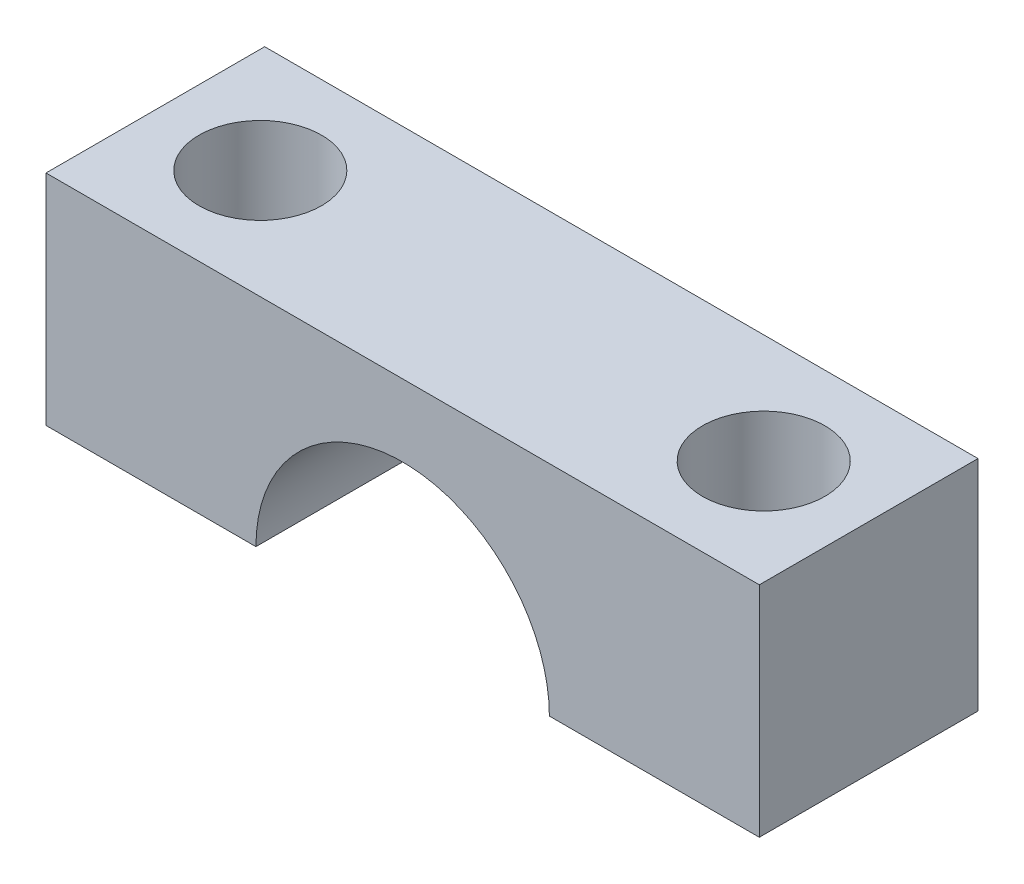
SolidWorks part; units mm, degrees
material "6061-T6 (SS)"
ref_plane "Front Plane" through (0, 0, 0) normal (0, 0, 1) x (1, 0, 0)
ref_plane "Top Plane" through (0, 0, 0) normal (0, 1, 0) x (1, 0, 0)
ref_plane "Right Plane" through (0, 0, 0) normal (1, 0, 0) x (0, 0, -1)
sketch "Sketch1" plane through (0, 0, 0) normal (0, 0, 1) x (1, 0, 0)
  line L1 (-8.155, -2.5) -> (8.155, -2.5)
  line L2 (-8.155, -2.5) -> (-8.155, 2.5)
  line L3 (-8.155, 2.5) -> (8.155, 2.5)
  line L4 (8.155, -2.5) -> (8.155, 2.5)
  line L5 (-8.155, -2.5) -> (8.155, 2.5) construction
  line L6 (-8.155, 2.5) -> (8.155, -2.5) construction
  point P0 (0, 0)
  dimension "D1" = 5
  dimension "D2" = 16.31
sketch "Sketch3" plane through (0, 0, 0) normal (0, 0, 1) x (1, 0, 0)
  line L0 (0, 0) -> (0, -2.5) construction
  line L1 (-8.155, -2.5) -> (8.155, -2.5) construction
  line L2 (-3.355, -2.5) -> (3.355, -2.5)
  line L3 (0, 0.855) -> (0, 2.5) construction
  line L4 (-8.155, 2.5) -> (8.155, 2.5) construction
  arc A0 (3.355, -2.5) -> (-3.355, -2.5) centre (0, -2.5) ccw
  point P8 (0, -2.5)
extrude "Boss-Extrude3" add sketch "Sketch1" against normal blind 5 contours L2 L3 L4 L1
extrude "Cut-Extrude9" cut sketch "Sketch3" against normal blind 5
sketch "Sketch4" plane through (0, 0, 0) normal (0, 1, 0) x (1, 0, 0)
  line L0 (0, 0) -> (0, 5) construction
  line L1 (-8.155, 0) -> (8.155, 0) construction
  line L2 (-8.155, 5) -> (8.155, 5) construction
  line L3 (0, 2.5) -> (5.755, 2.5) construction
  line L5 (0, 2.5) -> (-5.755, 2.5) construction
  circle A0 centre (-5.755, 2.5) radius 1.4
  circle A1 centre (5.755, 2.5) radius 1.4
extrude "Cut-Extrude10" cut sketch "Sketch4" against normal blind 2.5 and the other way blind 2.5 from offset 0
